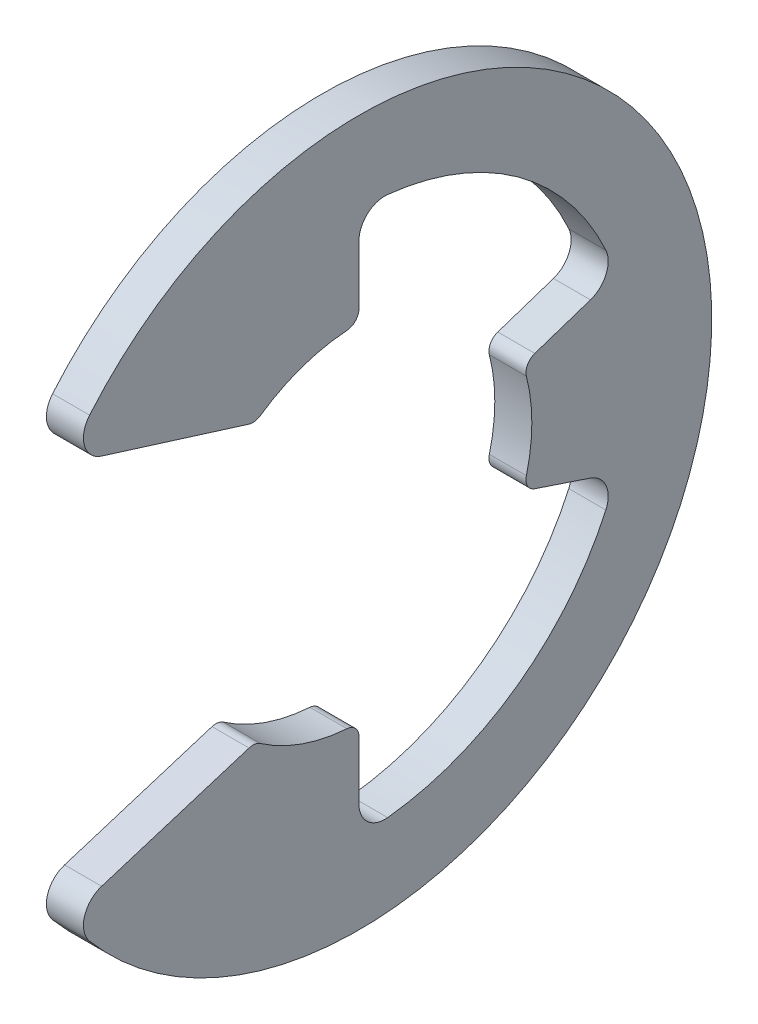
SolidWorks part; units mm, degrees
ref_plane "Front" through (0, 0, 0) normal (0, 0, 1) x (1, 0, 0)
ref_plane "Top" through (0, 0, 0) normal (0, 1, 0) x (1, 0, 0)
ref_plane "Right" through (0, 0, 0) normal (1, 0, 0) x (0, 0, -1)
sketch "Sketch1" plane through (0, 0, 0) normal (1, 0, 0) x (0, 0, -1)
  line L0 (-8.4234, -5.6809) -> (-2.987, -3.9827)
  line L1 (-8.4234, 5.6809) -> (-2.987, 3.9827)
  line L2 (0, -4.9784) -> (0, -7.8134)
  line L3 (0, 4.9784) -> (0, 7.8134)
  line L4 (4.7229, -1.5743) -> (7.4124, -2.4708)
  line L5 (4.7229, 1.5743) -> (7.4124, 2.4708)
  line L6 (0, 0) -> (-4.9784, 0) construction
  line L7 (4.7229, 1.5743) -> (4.7229, -1.5743) construction
  line L8 (0, -4.9784) -> (-2.987, -3.9827) construction
  line L9 (0, 10.16) -> (0, -10.16) construction
  circle A2 centre (0, 0) radius 4.9784 construction
  arc A3 (-8.4234, -5.6809) -> (-8.4234, 5.6809) centre (0, 0) ccw
  arc A4 (-2.987, -3.9827) -> (0, -4.9784) centre (0, 0) ccw
  arc A5 (-2.987, 3.9827) -> (0, 4.9784) centre (0, 0) cw
  arc A6 (4.7229, 1.5743) -> (4.7229, -1.5743) centre (0, 0) cw
  arc A7 (0, -7.8134) -> (7.4124, -2.4708) centre (0, 0) ccw
  arc A8 (7.4124, 2.4708) -> (0, 7.8134) centre (0, 0) ccw
  point P8 (0, 4.9784)
  point P12 (0, 10.16)
  dimension "Free Diameter" = 9.9568
  dimension "D1" = 7.8134
  dimension "Ring OD" = 20.32
  dimension "D2" = 5.8218
  dimension "D10" = 7.9654
sketch "Sketch4" plane through (0, 0, 0) normal (0, 0, 1) x (1, 0, 0)
  line L0 (-0.5334, 10.16) -> (0.5334, 10.16) construction
  point P3 (0, 10.16)
  dimension "Ring Thickness" = 1.0668
sketch "Sketch3" plane through (0, 0, 0) normal (1, 0, 0) x (0, 0, -1)
  line L6 (4.7229, -1.5743) -> (7.4124, -2.4708)
  line L7 (0, -7.8134) -> (0, -4.9784)
  line L8 (-2.987, -3.9827) -> (-8.4234, -5.6809)
  line L9 (-8.4234, 5.6809) -> (-2.987, 3.9827)
  line L10 (0, 4.9784) -> (0, 7.8134)
  line L11 (7.4124, 2.4708) -> (4.7229, 1.5743)
  line L12 (4.7229, -1.5743) -> (7.4124, -2.4708)
  line L13 (0, -7.8134) -> (0, -4.9784)
  line L14 (-2.987, -3.9827) -> (-8.4234, -5.6809)
  line L15 (-8.4234, 5.6809) -> (-2.987, 3.9827)
  line L16 (0, 4.9784) -> (0, 7.8134)
  line L17 (7.4124, 2.4708) -> (4.7229, 1.5743)
  arc A6 (0, -7.8134) -> (7.4124, -2.4708) centre (0, 0) ccw
  arc A7 (-2.987, -3.9827) -> (0, -4.9784) centre (0, 0) ccw
  arc A8 (-8.4234, -5.6809) -> (-8.4234, 5.6809) centre (0, 0) ccw
  arc A9 (0, 4.9784) -> (-2.987, 3.9827) centre (0, 0) ccw
  arc A10 (7.4124, 2.4708) -> (0, 7.8134) centre (0, 0) ccw
  arc A11 (4.7229, -1.5743) -> (4.7229, 1.5743) centre (0, 0) ccw
  arc A12 (0, -7.8134) -> (7.4124, -2.4708) centre (0, 0) ccw
  arc A13 (-2.987, -3.9827) -> (0, -4.9784) centre (0, 0) ccw
  arc A14 (-8.4234, -5.6809) -> (-8.4234, 5.6809) centre (0, 0) ccw
  arc A15 (0, 4.9784) -> (-2.987, 3.9827) centre (0, 0) ccw
  arc A16 (7.4124, 2.4708) -> (0, 7.8134) centre (0, 0) ccw
  arc A17 (4.7229, -1.5743) -> (4.7229, 1.5743) centre (0, 0) ccw
  dimension "D1" = 0
extrude "Boss-Extrude1" add sketch "Sketch3" along normal up to vertex (0.5334 mm away) and the other way up to vertex (0.5334 mm away) up to point (0.5334, 10.16, 0) other way up to point (-0.5334, 10.16, 0)
fillet "Fillet1" radius 0.7468 6 edges at (0, -7.8134, 0) (0, -2.4708, -7.4124) (0, 2.4708, -7.4124) (0, 7.8134, 0) (0, -5.6809, 8.4234) (0, 5.6809, 8.4234)
fillet "Fillet2" radius 0.3734 6 edges at (0, -4.9784, 0) (0, -3.9827, 2.987) (0, 1.5743, -4.7229) (0, -1.5743, -4.7229) (0, 3.9827, 2.987) (0, 4.9784, 0)
equation "\"D1@Sketch1\" =  ( \"Ring OD@Sketch1\" + \"Free Diameter@Sketch1\" )  / 3.875"
equation "\"D10@Sketch1\"=\"Free Diameter@Sketch1\" * .8"
equation "\"D1@Fillet1\"=\"Ring Thickness@Sketch4\"*.7"
equation "\"D1@Fillet2\"=\"D1@Fillet1\"/2"
